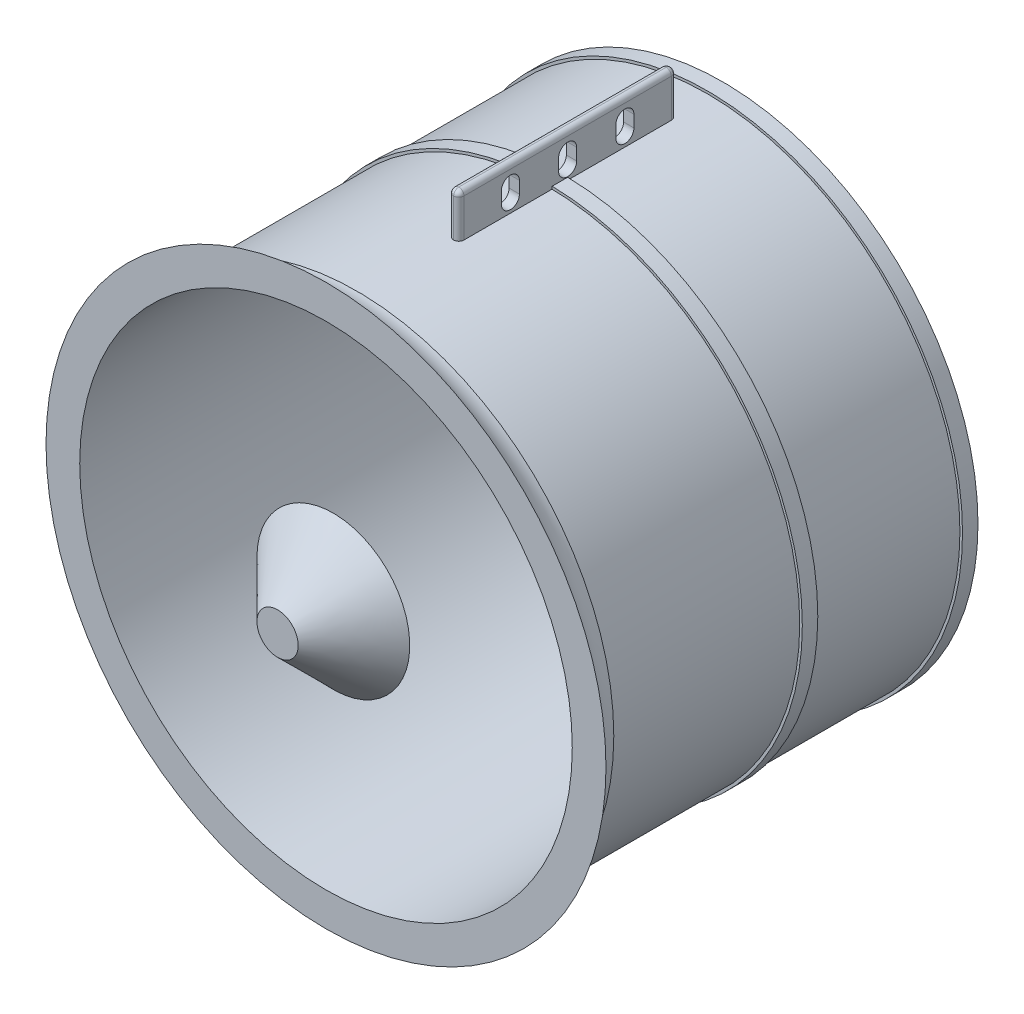
SolidWorks part; units mm, degrees
ref_plane "Front Plane" through (0, 0, 0) normal (0, 0, 1) x (1, 0, 0)
ref_plane "Top Plane" through (0, 0, 0) normal (0, 1, 0) x (1, 0, 0)
ref_plane "Right Plane" through (0, 0, 0) normal (1, 0, 0) x (0, 0, -1)
sketch "Sketch1" plane through (0, 0, 0) normal (1, 0, 0) x (0, 0, -1)
  line L0 (-9.1623, 0) -> (8.9822, 0) construction
  line L1 (72.4852, 49) -> (44.4252, 49)
  line L2 (75.4852, 49) -> (75.4852, 49.5)
  line L7 (75.4852, 49.5) -> (72.4852, 49.5)
  line L8 (72.4852, 49.5) -> (72.4852, 49)
  line L9 (44.4252, 49) -> (44.4252, 49.5)
  line L10 (44.4252, 49.5) -> (41.4252, 49.5)
  line L11 (41.4252, 49.5) -> (41.4252, 49)
  line L12 (4.5752, 49.8) -> (1.359, 49.8) construction
  line L13 (41.4252, 49) -> (4.5752, 49)
  line L14 (-10.8148, 0) -> (-10.8148, 4)
  line L15 (-1.4248, 49) -> (-1.4248, 47.75)
  line L16 (-1.4248, 47.75) -> (75.4852, 47.75)
  line L17 (75.4852, 47.75) -> (75.4852, 49)
  line L18 (-1.4248, 54.2857) -> (-1.4248, 47.75)
  line L19 (4.5752, 49.8) -> (4.5752, 49)
  line L20 (-10.8148, 4) -> (0, 14.8148)
  line L21 (0, 14.8148) -> (0, 0)
  line L22 (0, 0) -> (-10.8148, 0)
  arc A0 (4.5752, 49.8) -> (-1.4248, 54.2857) centre (4.5752, 56.0556) cw
  dimension "D9" = 1.4248
  dimension "D1" = 0.5
  dimension "D2" = 76.91
  dimension "D3" = 3
  dimension "D4" = 1.25
  dimension "D5" = 49
  dimension "D6" = 0.8
  dimension "D7" = 6.5357
  dimension "D8" = 6
  dimension "D10" = 36.85
  dimension "D11" = 45
  dimension "D12" = 86.3
  dimension "D13" = 4
revolve "Revolve1" add sketch "Sketch1" angle 360 about L0 region at (0, 48.61, -33.7048) region at (0, 5.2217, 4.3713)
sketch "Sketch2" plane through (0, 0, 0) normal (1, 0, 0) x (0, 0, -1)
  line L0 (41.4252, 49) -> (4.5752, 49) construction
  line L1 (23.3252, 49) -> (65.5252, 49)
  line L2 (23.3252, 49) -> (23.3252, 57.4)
  line L3 (23.3252, 57.4) -> (65.5252, 57.4)
  line L4 (65.5252, 49) -> (65.5252, 57.4)
  line L10 (75.4852, -49.5) -> (75.4852, 49.5) construction
  line L11 (0, 0) -> (91.2365, 0) construction
  line L16 (55.5252, 53.65) -> (55.5252, 51.35) construction
  line L17 (57.2752, 53.65) -> (57.2752, 51.35)
  line L18 (53.7752, 53.65) -> (53.7752, 51.35)
  line L19 (42.6752, 53.65) -> (42.6752, 51.35)
  line L20 (46.1752, 53.65) -> (46.1752, 51.35)
  line L21 (44.4252, 53.65) -> (44.4252, 51.35) construction
  line L22 (31.5752, 53.65) -> (31.5752, 51.35)
  line L23 (35.0752, 53.65) -> (35.0752, 51.35)
  line L24 (33.3252, 53.65) -> (33.3252, 51.35) construction
  line L25 (55.5252, -53.65) -> (55.5252, -51.35) construction
  line L26 (57.2752, -53.65) -> (57.2752, -51.35)
  line L27 (53.7752, -53.65) -> (53.7752, -51.35)
  line L28 (44.4252, -53.65) -> (44.4252, -51.35) construction
  line L29 (46.1752, -53.65) -> (46.1752, -51.35)
  line L30 (42.6752, -53.65) -> (42.6752, -51.35)
  line L31 (33.3252, -53.65) -> (33.3252, -51.35) construction
  line L32 (35.0752, -53.65) -> (35.0752, -51.35)
  line L33 (31.5752, -53.65) -> (31.5752, -51.35)
  line L34 (65.5252, -49) -> (65.5252, -57.4)
  line L35 (23.3252, -57.4) -> (65.5252, -57.4)
  line L36 (23.3252, -49) -> (23.3252, -57.4)
  line L37 (23.3252, -49) -> (65.5252, -49)
  arc A0 (57.2752, 53.65) -> (53.7752, 53.65) centre (55.5252, 53.65) ccw
  arc A1 (53.7752, 51.35) -> (57.2752, 51.35) centre (55.5252, 51.35) ccw
  arc A2 (46.1752, 53.65) -> (42.6752, 53.65) centre (44.4252, 53.65) ccw
  arc A3 (42.6752, 51.35) -> (46.1752, 51.35) centre (44.4252, 51.35) ccw
  arc A4 (35.0752, 53.65) -> (31.5752, 53.65) centre (33.3252, 53.65) ccw
  arc A5 (31.5752, 51.35) -> (35.0752, 51.35) centre (33.3252, 51.35) ccw
  arc A6 (57.2752, -53.65) -> (53.7752, -53.65) centre (55.5252, -53.65) cw
  arc A7 (53.7752, -51.35) -> (57.2752, -51.35) centre (55.5252, -51.35) cw
  arc A8 (46.1752, -53.65) -> (42.6752, -53.65) centre (44.4252, -53.65) cw
  arc A9 (42.6752, -51.35) -> (46.1752, -51.35) centre (44.4252, -51.35) cw
  arc A10 (35.0752, -53.65) -> (31.5752, -53.65) centre (33.3252, -53.65) cw
  arc A11 (31.5752, -51.35) -> (35.0752, -51.35) centre (33.3252, -51.35) cw
  point P12 (55.5252, -52.5)
  point P17 (55.5252, 52.5)
  point P26 (44.4252, 52.5)
  point P33 (33.3252, 52.5)
  point P41 (44.4252, -52.5)
  point P48 (33.3252, -52.5)
  dimension "D5" = 1.75
  dimension "D1" = 9.96
  dimension "D2" = 52.16
  dimension "D3" = 57.4
  dimension "D4" = 2.3
  dimension "D6" = 19.96
  dimension "D7" = 53.65
  dimension "D9" = 11.1
  dimension "D8" = 3
extrude "Boss-Extrude3" add sketch "Sketch2" along normal blind 1 and the other way blind 1 separate body
fillet "Fillet1" radius 1 6 edges at (1, 53.2, -23.3252) (-1, 53.2, -23.3252) (-1, 53.2, -65.5252) (1, 53.2, -65.5252) (1, 57.4, -44.4252) (-1, 57.4, -44.4252)
fillet "Fillet2" radius 1 6 edges at (-1, -57.4, -44.4252) (1, -57.4, -44.4252) (-1, -53.2, -65.5252) (1, -53.2, -65.5252) (1, -53.2, -23.3252) (-1, -53.2, -23.3252)
